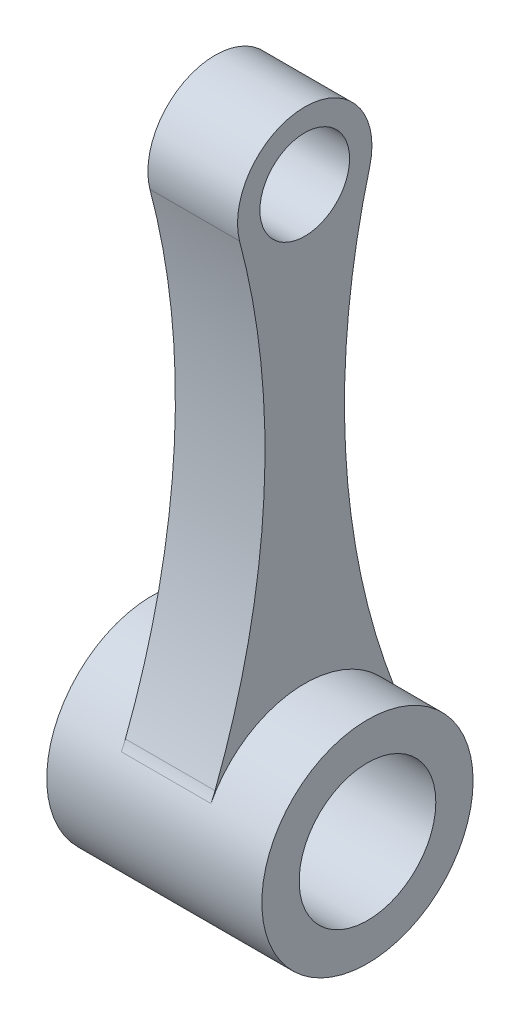
SolidWorks part; units mm, degrees
material "4032-T6"
ref_plane "Front Plane" through (0, 0, 0) normal (0, 0, 1) x (1, 0, 0)
ref_plane "Top Plane" through (0, 0, 0) normal (0, 1, 0) x (1, 0, 0)
ref_plane "Right Plane" through (0, 0, 0) normal (1, 0, 0) x (0, 0, -1)
sketch "Sketch1" plane through (0, 0, 0) normal (1, 0, 0) x (0, 0, -1)
  line L0 (0, 0) -> (0, 60)
  circle A0 centre (0, 0) radius 7.625
  circle A1 centre (0, 0) radius 11.7851
  circle A2 centre (0, 60) radius 5
  circle A3 centre (0, 60) radius 7.5
  arc A4 (-7.2754, 58.1783) -> (-10.2493, 5.8172) centre (-88.4035, 36.5211) cw
  arc A7 (7.2754, 58.1783) -> (10.2493, 5.8172) centre (88.4035, 36.5211) ccw
extrude "Boss-Extrude2" add sketch "Sketch1" against normal blind 12 and the other way blind 12 contours A7 A3 A4 A2 | A7 A3 L0 A1 | A3 A4 A1 L0 | A1 A0 region at (0, 9.8963, -5.7624) region at (0, 30.4595, 3.0337) region at (0, 30.4595, -3.0337) region at (0, 54.1915, 4.4017)
fillet "Fillet1" radius 10 2 edges at (0, 5.8172, -10.2493) (0, 5.8172, 10.2493)
sketch "Sketch2" plane through (12, 0, 0) normal (1, 0, 0) x (0, 0, -1)
  circle A0 centre (0, 60) radius 5
  circle A1 centre (0, 60) radius 7.5
  circle A2 centre (0, 0) radius 7.625
  circle A3 centre (0, 0) radius 11.7851
  arc A4 (-7.2754, 58.1783) -> (-10.0109, 6.431) centre (-88.4035, 36.5211) cw
  arc A5 (7.2754, 58.1783) -> (10.0109, 6.431) centre (88.4035, 36.5211) ccw
  circle M2 centre (0, 60) radius 5
  arc M3 (10.0109, 6.431) -> (7.2754, 58.1783) centre (88.4035, 36.5211) cw
  arc M4 (7.2754, 58.1783) -> (-7.2754, 58.1783) centre (0, 60) ccw
  arc M5 (-7.2754, 58.1783) -> (-10.0109, 6.431) centre (-88.4035, 36.5211) cw
  arc M6 (-10.0109, 6.431) -> (-10.4661, 5.4175) centre (-19.3468, 10.0145) cw
  arc M8 (10.4661, 5.4175) -> (10.0109, 6.431) centre (19.3468, 10.0145) cw
extrude "Cut-Extrude1" cut sketch "Sketch2" against normal blind 7 contours A3 A1 M8 M3 M5 M6 | A1 M5 M3 M4 M2 region at (12, 59.1082, -7.2331) region at (12, 30.4588, 0)
sketch "Sketch3" plane through (-12, 0, 0) normal (-1, 0, 0) x (0, 0, 1)
  circle A0 centre (0, 60) radius 5
  circle A1 centre (0, 60) radius 7.5
  circle A2 centre (0, 0) radius 7.625
  circle A3 centre (0, 0) radius 11.7851
  arc A4 (-7.2754, 58.1783) -> (-10.0109, 6.431) centre (-88.4035, 36.5211) cw
  arc A5 (7.2754, 58.1783) -> (10.0109, 6.431) centre (88.4035, 36.5211) ccw
  circle M2 centre (0, 60) radius 5
  arc M3 (-7.2754, 58.1783) -> (-10.0109, 6.431) centre (-88.4035, 36.5211) cw
  arc M4 (-10.0109, 6.431) -> (-10.4661, 5.4175) centre (-19.3468, 10.0145) cw
  arc M6 (10.4661, 5.4175) -> (10.0109, 6.431) centre (19.3468, 10.0145) cw
  arc M7 (10.0109, 6.431) -> (7.2754, 58.1783) centre (88.4035, 36.5211) cw
  arc M8 (7.2754, 58.1783) -> (-7.2754, 58.1783) centre (0, 60) ccw
extrude "Cut-Extrude2" cut sketch "Sketch3" against normal blind 7 contours A3 A1 M6 M7 M3 M4 | A1 M3 M7 M8 M2 region at (-12, 59.1082, 7.2331) region at (-12, 30.4588, 0)
